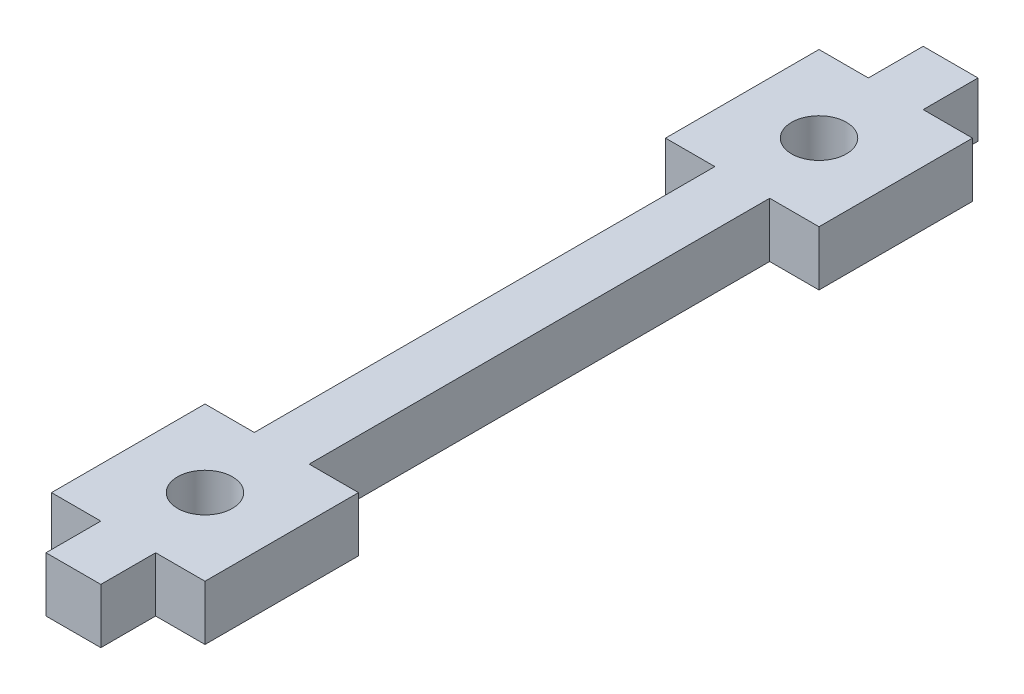
SolidWorks part; units mm, degrees
material "Pine"
ref_plane "Front Plane" through (0, 0, 0) normal (0, 0, 1) x (1, 0, 0)
ref_plane "Top Plane" through (0, 0, 0) normal (0, 1, 0) x (1, 0, 0)
ref_plane "Right Plane" through (0, 0, 0) normal (1, 0, 0) x (0, 0, -1)
sketch "Sketch1" plane through (0, 0, 0) normal (0, 1, 0) x (1, 0, 0)
  line L0 (0, 0) -> (0, 17.78)
  line L1 (0, 17.78) -> (-5.715, 17.78)
  line L2 (-5.715, 17.78) -> (-5.715, 24.13)
  line L3 (-5.715, 24.13) -> (-12.065, 24.13)
  line L4 (-12.065, 24.13) -> (-12.065, 17.78)
  line L5 (-12.065, 17.78) -> (-17.78, 17.78)
  line L6 (-17.78, 17.78) -> (-17.78, 0)
  line L8 (0, 17.78) -> (-17.78, 0) construction
  line L9 (-17.78, 0) -> (-12.065, 0)
  line L10 (-12.065, 0) -> (-12.065, -53.34)
  line L11 (-12.065, -53.34) -> (-17.78, -53.34)
  line L12 (-17.78, -53.34) -> (-17.78, -71.12)
  line L14 (0, -71.12) -> (0, -53.34)
  line L15 (0, -53.34) -> (-5.715, -53.34)
  line L16 (-5.715, -53.34) -> (-5.715, 0)
  line L17 (-5.715, 0) -> (0, 0)
  line L18 (-17.78, -71.12) -> (-12.065, -71.12)
  line L19 (-12.065, -71.12) -> (-12.065, -77.47)
  line L20 (-12.065, -77.47) -> (-5.715, -77.47)
  line L21 (-5.715, -77.47) -> (-5.715, -71.12)
  line L22 (-5.715, -71.12) -> (0, -71.12)
  line L23 (-17.78, -71.12) -> (0, -53.34) construction
  circle A0 centre (-8.89, 8.89) radius 3.175
  circle A1 centre (-8.89, -62.23) radius 3.175
  dimension "D5" = 6.35
  dimension "D15" = 6.35
  dimension "D1" = 17.78
  dimension "D2" = 17.78
  dimension "D3" = 6.35
  dimension "D4" = 6.35
  dimension "D6" = 17.78
  dimension "D7" = 53.34
  dimension "D8" = 17.78
  dimension "D9" = 5.715
  dimension "D10" = 6.35
  dimension "D11" = 53.34
  dimension "D12" = 6.35
  dimension "D13" = 5.715
  dimension "D14" = 5.715
extrude "Boss-Extrude1" add sketch "Sketch1" along normal blind 6.35
